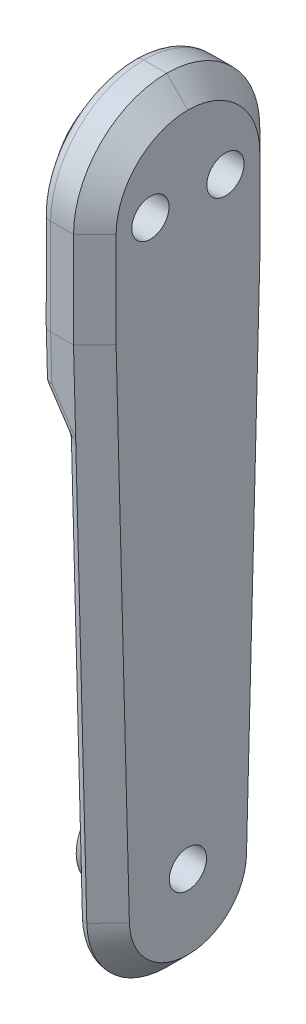
SolidWorks part; units mm, degrees
material "ABS"
ref_plane "Front Plane" through (0, 0, 0) normal (0, 0, 1) x (1, 0, 0)
ref_plane "Top Plane" through (0, 0, 0) normal (0, 1, 0) x (1, 0, 0)
ref_plane "Right Plane" through (0, 0, 0) normal (1, 0, 0) x (0, 0, -1)
sketch "Sketch1" plane through (0, 0, 0) normal (1, 0, 0) x (0, 0, -1)
  line L1 (-10, 10) -> (10, 10)
  line L2 (-10, 10) -> (-10, -10)
  line L3 (-10, -10) -> (10, -10)
  line L4 (10, 10) -> (10, -10)
  line L5 (-10, 10) -> (10, -10) construction
  line L6 (-10, -10) -> (10, 10) construction
  point P0 (0, 0)
  dimension "D1" = 20
  dimension "D2" = 20
extrude "Boss-Extrude1" add sketch "Sketch1" along normal blind 20
sketch "Sketch2" plane through (20, 0, 0) normal (1, 0, 0) x (0, 0, -1)
  line L1 (-22.5, 35) -> (22.5, 35)
  line L2 (-22.5, 35) -> (-22.5, -35)
  line L3 (-22.5, -35) -> (22.5, -35)
  line L4 (22.5, 35) -> (22.5, -35)
  line L5 (-22.5, 35) -> (22.5, -35) construction
  line L6 (-22.5, -35) -> (22.5, 35) construction
  point P0 (0, 0)
  dimension "D1" = 45
  dimension "D2" = 70
extrude "Boss-Extrude2" add sketch "Sketch2" along normal blind 10.3
sketch "Sketch4" plane through (30.3, 0, 0) normal (1, 0, 0) x (0, 0, -1)
  line L0 (0, 7.65) -> (0, 8.1702) construction
  line L1 (7.65, 7.65) -> (-7.65, 7.65) construction
  line L17 (3.6, -26.55) -> (-3.6, -26.55) construction
  line L18 (-7.65, 7.65) -> (7.65, 7.65) construction
  line L22 (-7.65, 7.65) -> (-7.65, -27.55) construction
  line L23 (-7.65, -27.55) -> (7.65, -27.55) construction
  line L24 (7.65, 7.65) -> (7.65, -27.55) construction
  line L25 (-7.65, 7.65) -> (7.65, -27.55) construction
  line L26 (-7.65, -27.55) -> (7.65, 7.65) construction
  line L27 (3.6, -26.55) -> (3.6, -28.55) construction
  line L28 (3.6, -28.55) -> (-3.6, -28.55) construction
  line L29 (-3.6, -26.55) -> (-3.6, -28.55) construction
  line L30 (3.6, -26.55) -> (-3.6, -28.55) construction
  line L31 (3.6, -28.55) -> (-3.6, -26.55) construction
  line L34 (3.6, -28.55) -> (-3.6, -28.55)
  line L35 (-3.6, -28.55) -> (-3.6, -7.3118)
  line L36 (3.6, -28.55) -> (3.6, -7.3118)
  arc A1 (3.6, -6.75) -> (-3.6, -6.75) centre (0, 0) ccw construction
  arc A2 (3.6, -7.3118) -> (-3.6, -7.3118) centre (0, 0) ccw
  point P1 (0, -27.55)
  point P7 (0, -13.75)
  point P10 (0, 7.65)
  point P14 (0, -9.95)
  dimension "D1" = 15.3
  dimension "D5" = 2
  dimension "D2" = 15.3
  dimension "D3" = 35.2
  dimension "D4" = 7.2
extrude "Cut-Extrude1" cut sketch "Sketch4" against normal blind 5.8
fillet "Fillet1" radius 3.6 2 edges at (27.4, -28.55, 3.6) (27.4, -28.55, -3.6)
fillet "Fillet2" radius 10 2 edges at (27.4, -7.3118, 3.6) (27.4, -7.3118, -3.6)
sketch "Sketch5" plane through (0, 0, 0) normal (-1, 0, 0) x (0, 0, 1)
  circle A0 centre (0, 0) radius 1.75
  dimension "D1" = 3.5
extrude "Cut-Extrude2" cut sketch "Sketch5" against normal through all
sketch "Sketch6" plane through (24.5, 0, 0) normal (1, 0, 0) x (0, 0, -1)
  line L0 (0, -19.35) -> (0, 0) construction
  line L1 (0, -25.65) -> (0, -23.15) construction
  line L2 (0, -23.15) -> (0, -21.85) construction
  line L3 (0, -21.85) -> (0, -19.35) construction
  line L5 (0, 0) -> (1.164, 0) construction
  line L6 (0, 0) -> (0, -9.35) construction
  line L7 (0, -9.35) -> (1.164, -9.35) construction
  line L8 (1.164, 0) -> (1.164, -9.35) construction
  line L9 (0, 0) -> (1.164, -9.35) construction
  line L10 (0, -9.35) -> (1.164, 0) construction
  circle A0 centre (0, -20.6) radius 1.75
  circle A1 centre (0, -9.35) radius 1.75 construction
  point P11 (0.582, -4.675)
  dimension "D5" = 3.5
  dimension "D6" = 9.35
  dimension "D7" = 3.5
  dimension "D1" = 19.35
  dimension "D2" = 2.5
  dimension "D3" = 1.3
  dimension "D4" = 2.5
extrude "Cut-Extrude3" cut sketch "Sketch6" against normal up to next
sketch "Sketch13" plane through (0, 0, 0) normal (-1, 0, 0) x (0, 0, 1)
  line L1 (-10, 10) -> (10, 10)
  line L2 (-10, 10) -> (-10, -10)
  line L3 (-10, -10) -> (10, -10)
  line L4 (10, 10) -> (10, -10)
extrude "Cut-Extrude9" cut sketch "Sketch13" against normal up to surface (20 mm away) up to face at (20, -20.6, -1.75)
sketch "Sketch14" plane through (20, 0, 0) normal (-1, 0, 0) x (0, 0, 1)
  circle A5 centre (0, 0) radius 11
  dimension "D2" = 22
extrude "Boss-Extrude3" add sketch "Sketch14" along normal blind 7 contours A5
sketch "Sketch15" plane through (0, 35, 0) normal (0, 1, 0) x (1, 0, 0)
  line L1 (20, 22.5) -> (30.3, 22.5)
  line L2 (20, 22.5) -> (20, -22.5)
  line L3 (20, -22.5) -> (30.3, -22.5)
  line L4 (30.3, 22.5) -> (30.3, -22.5)
extrude "Cut-Extrude10" cut sketch "Sketch15" against normal blind 12.5
sketch "Sketch18" plane through (0, -35, 0) normal (0, -1, 0) x (1, 0, 0)
  line L1 (20, 22.5) -> (30.3, 22.5)
  line L2 (20, 22.5) -> (20, -22.5)
  line L3 (20, -22.5) -> (30.3, -22.5)
  line L4 (30.3, 22.5) -> (30.3, -22.5)
  line L5 (30.3, 22.5) -> (20, 22.5) construction
  line L6 (30.3, 22.5) -> (30.3, -22.5) construction
extrude "Boss-Extrude4" add sketch "Sketch18" along normal blind 95.5
sketch "Sketch20" plane through (20, 0, 0) normal (-1, 0, 0) x (0, 0, 1)
  line L0 (0, 0) -> (0, -100) construction
  line L1 (22.5, 22.5) -> (22.5, -130.5) construction
  line L2 (-22.5, -130.5) -> (22.5, -130.5)
  line L3 (-22.5, -130.5) -> (-22.5, -33.5)
  line L4 (-22.5, -33.5) -> (22.5, -33.5)
  line L5 (22.5, -130.5) -> (22.5, -33.5)
  dimension "D1" = 100
  dimension "D2" = 97
extrude "Cut-Extrude12" cut sketch "Sketch20" against normal blind 4.3
sketch "Sketch21" plane through (24.3, 0, 0) normal (-1, 0, 0) x (0, 0, 1)
  line L0 (0, -130.5) -> (0, -109.5) construction
  line L1 (-22.5, -130.5) -> (22.5, -130.5) construction
  circle A0 centre (0, -109.5) radius 8
  dimension "D2" = 16
  dimension "D1" = 21
extrude "Boss-Extrude5" add sketch "Sketch21" along normal blind 15.6
sketch "Sketch24" plane through (13, 0, 0) normal (-1, 0, 0) x (0, 0, 1)
  circle A2 centre (0, 0) radius 8
  circle A3 centre (0, 0) radius 8
  dimension "D1" = 3
extrude "Cut-Extrude14" cut sketch "Sketch24" against normal blind 7.6
sketch "Sketch25" plane through (0, 0, -22.5) normal (0, 0, -1) x (-1, 0, 0)
  line L6 (-24.3, -130.5) -> (-24.3, -33.5)
  line L7 (-24.3, -33.5) -> (-20, -33.5)
  line L8 (-20, -33.5) -> (-20, 22.5)
  line L9 (-20, 22.5) -> (-30.3, 22.5)
  line L10 (-30.3, 22.5) -> (-30.3, -130.5)
  line L11 (-30.3, -130.5) -> (-24.3, -130.5)
  line L12 (-24.3, -130.5) -> (-24.3, -33.5)
  line L13 (-24.3, -33.5) -> (-20, -33.5)
  line L14 (-20, -33.5) -> (-20, 22.5)
  line L15 (-20, 22.5) -> (-30.3, 22.5)
  line L16 (-30.3, 22.5) -> (-30.3, -130.5)
  line L17 (-30.3, -130.5) -> (-24.3, -130.5)
  dimension "D1" = 0
extrude "Cut-Extrude15" cut sketch "Sketch25" against normal blind 5
sketch "Sketch26" plane through (0, 0, 22.5) normal (0, 0, 1) x (1, 0, 0)
  line L6 (20, 22.5) -> (20, -33.5)
  line L7 (20, -33.5) -> (24.3, -33.5)
  line L8 (24.3, -33.5) -> (24.3, -130.5)
  line L9 (24.3, -130.5) -> (30.3, -130.5)
  line L10 (30.3, -130.5) -> (30.3, 22.5)
  line L11 (30.3, 22.5) -> (20, 22.5)
  line L12 (20, 22.5) -> (20, -33.5)
  line L13 (20, -33.5) -> (24.3, -33.5)
  line L14 (24.3, -33.5) -> (24.3, -130.5)
  line L15 (24.3, -130.5) -> (30.3, -130.5)
  line L16 (30.3, -130.5) -> (30.3, 22.5)
  line L17 (30.3, 22.5) -> (20, 22.5)
  dimension "D1" = 0
extrude "Cut-Extrude16" cut sketch "Sketch26" against normal blind 5
sketch "Sketch28" plane through (20, 0, 0) normal (-1, 0, 0) x (0, 0, 1)
  line L0 (0, 11) -> (0, 18) construction
  line L1 (17.5, 22.5) -> (17.5, -33.5) construction
  line L2 (-17.5, 22.5) -> (17.5, 22.5)
  line L3 (-17.5, 22.5) -> (-17.5, 18)
  line L4 (-17.5, 18) -> (17.5, 18)
  line L5 (17.5, 22.5) -> (17.5, 18)
  circle A0 centre (0, 0) radius 11 construction
  dimension "D1" = 7
extrude "Cut-Extrude17" cut sketch "Sketch28" against normal through all
sketch "Sketch31" plane through (13, 0, 0) normal (-1, 0, 0) x (0, 0, 1)
  line L0 (0, 0) -> (-3.1, 0) construction
  line L1 (-3.1, 0) -> (-11, 0) construction
  line L2 (0, 0) -> (3.1, 0) construction
  line L3 (3.1, 0) -> (11, 0) construction
  circle A1 centre (0, 0) radius 11 construction
  circle A2 centre (-7.05, 0) radius 3.9
  circle A3 centre (7.05, 0) radius 3.9
  dimension "D2" = 7.8
  dimension "D4" = 7.8
  dimension "D1" = 3.1
  dimension "D3" = 3.1
extrude "Boss-Extrude6" add sketch "Sketch31" against normal up to surface (7.6 mm away) up to face at (20.6, 0, 8)
sketch "Sketch36" plane through (30.3, 0, 0) normal (1, 0, 0) x (0, 0, -1)
  line L1 (-10.2624, 8.7262) -> (10.2624, 8.7262)
  line L2 (-10.2624, 8.7262) -> (-10.2624, -29.3718)
  line L3 (-10.2624, -29.3718) -> (10.2624, -29.3718)
  line L4 (10.2624, 8.7262) -> (10.2624, -29.3718)
  point P5 (0, 8.7262)
  arc M7 (-6.1069, -5.3971) -> (6.1069, -5.3971) centre (0, 0) cw
  arc M8 (6.1069, -5.3971) -> (3.6, -12.0193) centre (13.6, -12.0193) ccw
  line M9 (3.6, -12.0193) -> (3.6, -24.95)
  arc M10 (3.6, -24.95) -> (0, -28.55) centre (0, -24.95) cw
  arc M11 (0, -28.55) -> (-3.6, -24.95) centre (0, -24.95) cw
  line M12 (-3.6, -24.95) -> (-3.6, -12.0193)
  arc M13 (-3.6, -12.0193) -> (-6.1069, -5.3971) centre (-13.6, -12.0193) ccw
  arc M14 (-6.1069, -5.3971) -> (6.1069, -5.3971) centre (0, 0) cw
  arc M16 (-6.1069, -5.3971) -> (6.1069, -5.3971) centre (0, 0) cw
extrude "Boss-Extrude7" add sketch "Sketch36" against normal blind 6 contours M16 M14 M13 M12 M11 M10 M9 M8 M7 | L4 L1 L2 L3 M16 M7 M8 M9 M10 M11 M12 M13 M14 | L2 L1 L4 L3 region at (30.3, 8.2935, 0) region at (30.3, -7.2742, 0)
sketch "Sketch33" plane through (13, 0, 0) normal (-1, 0, 0) x (0, 0, 1)
  line L0 (-3.15, 0) -> (-10.95, 0) construction
  line L1 (3.15, 0) -> (10.95, 0) construction
  arc A0 (-6.9853, -3.8995) -> (-6.9853, 3.8995) centre (-7.05, 0) ccw construction
  arc A1 (6.9853, 3.8995) -> (6.9853, -3.8995) centre (7.05, 0) ccw construction
  circle A2 centre (-7.05, 0) radius 1.75
  circle A3 centre (7.05, 0) radius 1.75
  dimension "D3" = 3.5
  dimension "D4" = 3.5
  dimension "D1" = 7.8
  dimension "D2" = 7.8
extrude "Cut-Extrude19" cut sketch "Sketch33" against normal through all contours A2 | A3
fillet "Fillet8" radius 17.5 2 edges at (25.15, 18, 17.5) (25.15, 18, -17.5)
sketch "Sketch23" plane through (8.7, 0, 0) normal (-1, 0, 0) x (0, 0, 1)
  circle A3 centre (0, -109.5) radius 1.75
  dimension "D1" = 3.5
extrude "Cut-Extrude13" cut sketch "Sketch23" against normal through all contours A3
sketch "Sketch35" plane through (0, -130.5, 0) normal (0, -1, 0) x (1, 0, 0)
  line L4 (30.3, -17.5) -> (30.3, 17.5)
  line L5 (30.3, 17.5) -> (24.3, 17.5)
  line L6 (24.3, 17.5) -> (24.3, -17.5)
  line L7 (24.3, -17.5) -> (30.3, -17.5)
  line L8 (30.3, -17.5) -> (30.3, 17.5)
  line L9 (30.3, 17.5) -> (24.3, 17.5)
  line L10 (24.3, 17.5) -> (24.3, -17.5)
  line L11 (24.3, -17.5) -> (30.3, -17.5)
  dimension "D1" = 0
extrude "Cut-Extrude21" cut sketch "Sketch35" against normal blind 3
chamfer "Chamfer6" distance 110 angle 1.5 2 edges at (27.3, -127.5, -17.5) (27.3, -127.5, 17.5) first distance on face at (24.8667, -53.5, -17.5) first distance on face at (24.8667, -53.5, 17.5)
fillet "Fillet11" radius 15 2 edges at (27.3, -127.5, 14.6195) (27.3, -127.5, -14.6195)
chamfer "Chamfer9" distance 7 angle 32 1 edges at (20, -33.5, 0) first distance on face at (20, -20.6, -1.75)
sketch "Sketch38" plane through (13, 0, 0) normal (-1, 0, 0) x (0, 0, 1)
  circle A1 centre (0, 0) radius 11
  circle A2 centre (0, 0) radius 11
  dimension "D1" = 0
extrude "Cut-Extrude22" cut sketch "Sketch38" against normal blind 3
sketch "Sketch40" plane through (20, 0, 0) normal (-1, 0, 0) x (0, 0, 1)
  circle A1 centre (0, -20.6) radius 1.75
  circle A2 centre (0, -20.6) radius 1.75
  arc A4 (-6.9853, -3.8995) -> (-6.9853, 3.8995) centre (-7.05, 0) ccw
  arc A5 (-6.9853, -3.8995) -> (6.9853, -3.8995) centre (0, 0) ccw
  arc A6 (6.9853, 3.8995) -> (6.9853, -3.8995) centre (7.05, 0) ccw
  arc A7 (6.9853, 3.8995) -> (-6.9853, 3.8995) centre (0, 0) ccw
  arc A8 (-6.9853, -3.8995) -> (-6.9853, 3.8995) centre (-7.05, 0) ccw
  arc A9 (-6.9853, -3.8995) -> (6.9853, -3.8995) centre (0, 0) ccw
  arc A10 (6.9853, 3.8995) -> (6.9853, -3.8995) centre (7.05, 0) ccw
  arc A11 (6.9853, 3.8995) -> (-6.9853, 3.8995) centre (0, 0) ccw
  dimension "D1" = 0
  dimension "D2" = 0
extrude "Boss-Extrude8" add sketch "Sketch40" against normal through all
sketch "Sketch41" plane through (8.7, 0, 0) normal (-1, 0, 0) x (0, 0, 1)
  circle A1 centre (0, -109.5) radius 8
  circle A2 centre (0, -109.5) radius 8
  dimension "D1" = 0
extrude "Cut-Extrude23" cut sketch "Sketch41" against normal blind 8.6 contours A2
sketch "Sketch42" plane through (30.3, 0, 0) normal (1, 0, 0) x (0, 0, -1)
  circle A0 centre (-7.05, 0) radius 3.5
  circle A1 centre (7.05, 0) radius 3.5
  circle A2 centre (0, -109.5) radius 3.5
  dimension "D1" = 7
  dimension "D2" = 7
  dimension "D3" = 7
extrude "Cut-Extrude24" cut sketch "Sketch42" against normal blind 8
fillet "Fillet14" radius 2 2 edges at (24.3, -33.3814, 0) (20, -26.5, 0)
fillet "Fillet15" radius 2 1 edges at (24.3, -109.5, -8)
fillet "Fillet16" radius 1 1 edges at (20, 0, -11)
chamfer "Chamfer10" distance 4 angle 45 9 edges at (30.3, -8.5, -17.5) (30.3, 12.8744, -12.3744) (30.3, 12.8744, 12.3744) (30.3, -8.5, 17.5) (30.3, -65.1963, -16.251) (30.3, -123.2445, -10.4741) (30.3, -65.1963, 16.251) (30.3, -127.5, 0) (30.3, -123.2445, 10.4741)
fillet "Fillet13" radius 2 17 edges at (24.3, -73.4238, -16.0356) (24.3, -123.2445, -10.4741) (24.3, -123.2445, 10.4741) (20, -8.5, 17.5) (20, -8.5, -17.5) (20, 12.8744, -12.3744) (22.15, -29.9407, -17.1742) (24.3, -73.4238, 16.0356) (22.15, -29.9407, 17.1742) (20, 12.8744, 12.3744) (20, -21.7133, 17.3897) (20, -21.7133, -17.3897) (24.3, -127.5, 0) (20.0775, -26.4778, -17.2649) (24.2225, -33.4037, -17.0835) (24.2225, -33.4037, 17.0835) (20.0775, -26.4778, 17.2649)
